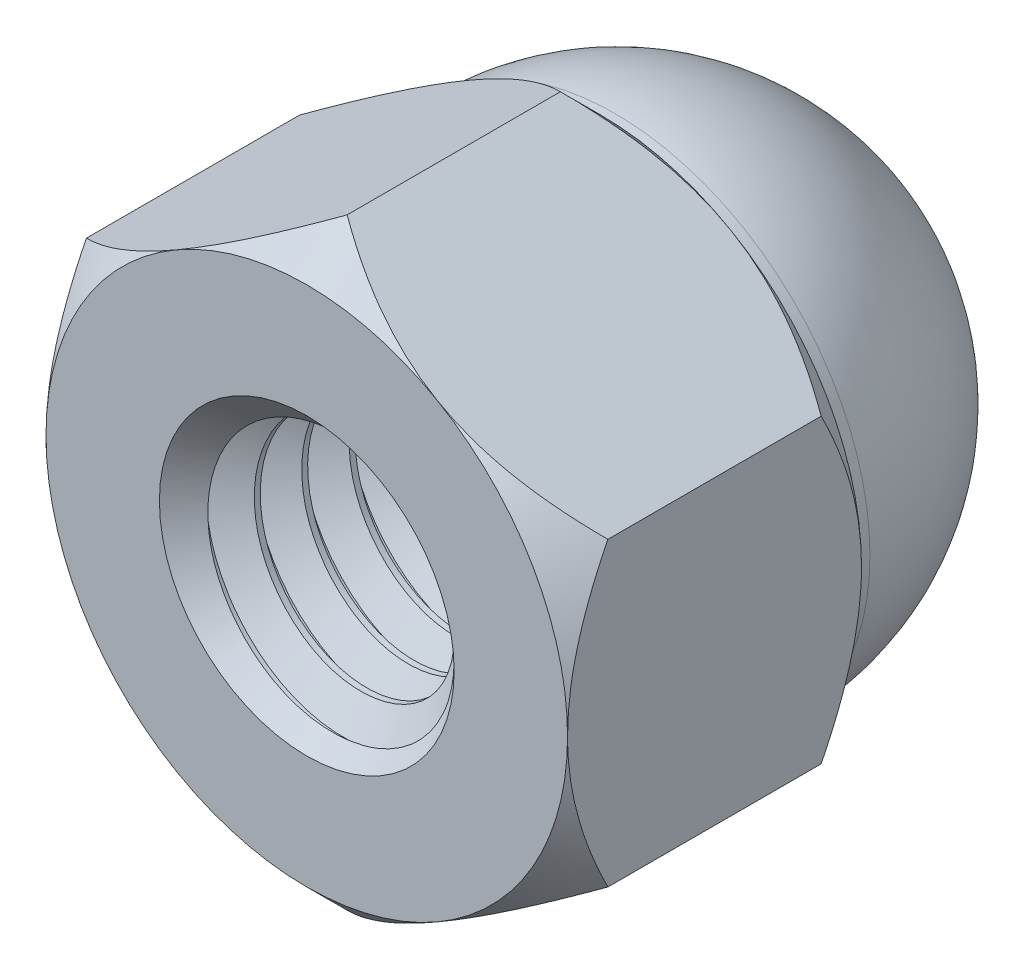
SolidWorks part; units mm, degrees
ref_plane "Front Plane" through (0, 0, 0) normal (0, 0, 1) x (1, 0, 0)
ref_plane "Top Plane" through (0, 0, 0) normal (0, 1, 0) x (1, 0, 0)
ref_plane "Right Plane" through (0, 0, 0) normal (1, 0, 0) x (0, 0, -1)
sketch "Sketch1" plane through (0, 0, 0) normal (-1, 0, 0) x (0, 0, 1)
  line L0 (-3, 0) -> (3, 0) construction
  line L1 (-3, 0) -> (-3, 2.75) construction
  line L2 (3, 2.75) -> (-3, 2.75) construction
  line L3 (3, 1.5) -> (-0.8, 1.5) construction
  line L4 (3, 0) -> (3, 2.75) construction
  line L5 (-0.8, 1.5) -> (-0.8, 0) construction
  line L7 (-0.8, 1.5) -> (-1.2019, 0) construction
  line L8 (3.4687, 1.5541) -> (3.2187, 1.1211) construction
  line L9 (3.2187, 1.1211) -> (2.9687, 1.5541) construction
  line L10 (2.9687, 1.5541) -> (3.4687, 1.5541) construction
  line L11 (3.2187, 1.1211) -> (3.2187, 1.1752) construction
  line L12 (3.2187, 1.5541) -> (3.2187, 1.5) construction
  line L13 (3.4375, 1.5) -> (3, 1.5) construction
  line L14 (3.1875, 1.1752) -> (3.25, 1.1752) construction
  line L15 (3.2187, 1.5271) -> (2.9844, 1.5271) construction
  line L16 (3.2187, 1.5271) -> (3.4531, 1.5271) construction
  arc A2 (-3, 0) -> (-0.25, 2.75) centre (-0.25, 0) cw construction
  point P3 (0, 0)
  point P23 (-0.1, 2.75)
  dimension "Height" = 6
  dimension "Width" = 5.5
  dimension "Thread Depth" = 3.8
  dimension "Thread OD" = 3
  dimension "Thread Tip Angle" = 75
  dimension "Thread Pitch" = 0.5
  dimension "D1" = 0.0625
  dimension "Hex Thickness (m)" = 3.1
ref_plane "Plane1" through (0, 0, 3) normal (0, 0, 1) x (1, 0, 0)
ref_plane "Plane2" through (0, 0, -0.1) normal (0, 0, 1) x (1, 0, 0)
ref_plane "Plane3" through (0, 0, -0.8) normal (0, 0, 1) x (1, 0, 0)
sketch "Sketch7" plane through (0, 0, 3) normal (0, 0, 1) x (1, 0, 0)
  line L1 (0, 3.1754) -> (-2.75, 1.5877)
  line L2 (-2.75, 1.5877) -> (-2.75, -1.5877)
  line L3 (-2.75, -1.5877) -> (0, -3.1754)
  line L4 (0, -3.1754) -> (2.75, -1.5877)
  line L5 (2.75, -1.5877) -> (2.75, 1.5877)
  line L6 (2.75, 1.5877) -> (0, 3.1754)
  circle A0 centre (0, 0) radius 2.75 construction
  point P0 (0, 2.75)
extrude "Boss-Extrude2" add sketch "Sketch7" against normal up to vertex (3.1 mm away) up to point (0, 2.75, -0.1)
sketch "Sketch8" plane through (0, 0, 3) normal (0, 0, 1) x (1, 0, 0)
  circle A0 centre (0, 0) radius 2.75
extrude "Cut-Extrude3" cut sketch "Sketch8" against normal through all draft 45 flip side to cut
sketch "Sketch9" plane through (0, 0, -0.1) normal (0, 0, 1) x (1, 0, 0)
  circle A1 centre (0, 0) radius 2.75
  circle A2 centre (0, 0) radius 2.75
  dimension "D1" = 0
extrude "Cut-Extrude4" cut sketch "Sketch9" along normal through all draft 45 flip side to cut
sketch "Sketch10" plane through (0, 0, 0) normal (1, 0, 0) x (0, 0, -1)
  line L0 (0.25, 2.75) -> (0.1, 2.75)
  line L1 (3, 0) -> (-3, 0) construction
  line L3 (3, 0) -> (0.1, 0)
  line L4 (0.1, 2.75) -> (0.1, 0)
  arc A0 (3, 0) -> (0.25, 2.75) centre (0.25, 0) ccw construction
  arc A4 (3, 0) -> (0.25, 2.75) centre (0.25, 0) ccw
revolve "Revolve1" add sketch "Sketch10" angle 360 about L0
sketch "Sketch16" plane through (0, 0, 0) normal (0, 0, 1) x (1, 0, 0)
  line L0 (0, 0) -> (0, -1.5) construction
  line L1 (0, 0) -> (0.574, -1.3858) construction
  circle A0 centre (0, 0) radius 1.5 construction
  point P3 (0.574, -1.3858)
  dimension "D1" = 22.5
sketch "Sketch17" plane through (0, 0, 0) normal (1, 0, 0) x (0, 0, -1)
  line L0 (0.8, 1.5) -> (1.2019, 0) construction
  line L1 (-3, 1.5) -> (0.8, 1.5) construction
  line L2 (0.8, 1.5) -> (1.2019, 0)
  line L3 (-3, 1.5) -> (0.8, 1.5)
  line L4 (1.2019, 0) -> (0.8, -1.5)
  line L5 (0.8, -1.5) -> (-3, -1.5)
sketch "Sketch11" plane through (0, 0, 0) normal (1, 0, 0) x (0, 0, -1)
  line L2 (-3, 0) -> (-3, 2.75) construction
  line L3 (-3, 1.5) -> (0.8, 1.5) construction
  line L6 (-3, 0) -> (-3, 1.5)
  line L7 (-3, 1.5) -> (0.8, 1.5)
  line L8 (0.8, 1.5) -> (1.2019, 0) construction
  line L9 (0.8, 1.5) -> (1.2019, 0)
  line L10 (3, 0) -> (-3, 0) construction
  line L11 (1.2019, 0) -> (-3, 0)
revolve "Cut-Revolve1" cut sketch "Sketch11" angle 360 about L0
sketch "Sketch12" plane through (0, 0, 3) normal (0, 0, 1) x (1, 0, 0)
  circle A0 centre (0, 0) radius 1.5
  point P0 (0, 1.5)
curve "Helix/Spiral1" pitch 0.5 height 4.3 turns 8.6
sketch "Sketch13" plane through (0, 0, 0) normal (1, 0, 0) x (0, 0, -1)
  line L0 (-3.4531, 1.5271) -> (-3.25, 1.1752)
  line L1 (-3.25, 1.1752) -> (-3.1875, 1.1752)
  line L2 (-3.1875, 1.1752) -> (-2.9844, 1.5271)
  line L3 (-2.9844, 1.5271) -> (-3.4531, 1.5271)
sweep "Sweep1" add profiles "Sketch13" path "Helix/Spiral1"
sketch "Sketch14" plane through (0, 0, 0) normal (1, 0, 0) x (0, 0, -1)
  line L0 (3, 0) -> (3, 2.75) construction
  line L1 (0.25, 2.6891) -> (0.1, 2.6891)
  line L2 (3, 0.75) -> (3, 2.75) construction
  line L4 (3, 0.75) -> (2.8782, 0.75) construction
  line L5 (0.8, 1.5) -> (0.8, 0) construction
  line L7 (3.1218, 2.75) -> (3.1218, 0.75)
  line L8 (3.1218, 0.75) -> (3, 0.75) construction
  line L10 (3.1218, 0.75) -> (3.1218, 0)
  line L12 (3.1218, 0) -> (3, 0)
  line L13 (3, 0) -> (-3, 0) construction
  line L14 (3, 2.75) -> (0.25, 2.75)
  line L15 (3, 2.75) -> (3.1218, 2.75)
  line L17 (0.25, 2.75) -> (0.25, 2.6282) construction
  line L21 (3, 0) -> (3, -2.8136) construction
  line L22 (-3, 2.75) -> (3, 2.75) construction
  line L23 (0.1, 2.75) -> (0.1, 2.3816) construction
  line L24 (0.25, 2.75) -> (0.1, 2.75)
  line L25 (0.1, 2.75) -> (0.1, 2.6891)
  line L26 (0.25, 2.75) -> (0.25, -2.75) construction
  arc A0 (3, 0) -> (0.25, 2.6891) centre (0.25, -0.0616) ccw
  point P9 (0.8, 0.75)
revolve "Cut-Revolve4" cut sketch "Sketch14" angle 360 about L0
sketch "Sketch15" plane through (0, 0, 3) normal (0, 0, 1) x (1, 0, 0)
  circle A0 centre (0, 0) radius 1.5541
extrude "Cut-Extrude5" cut sketch "Sketch15" against normal through all draft 45 and the other way through all draft 45
equation "\"D1@Sketch1\" = \"Thread Pitch@Sketch1\" / 8"
equation "\"D3@Helix/Spiral1\" = \"Thread Depth@Sketch1\" + \"Thread Pitch@Sketch1\""
equation "\"D4@Helix/Spiral1\" = \"Thread Pitch@Sketch1\""
